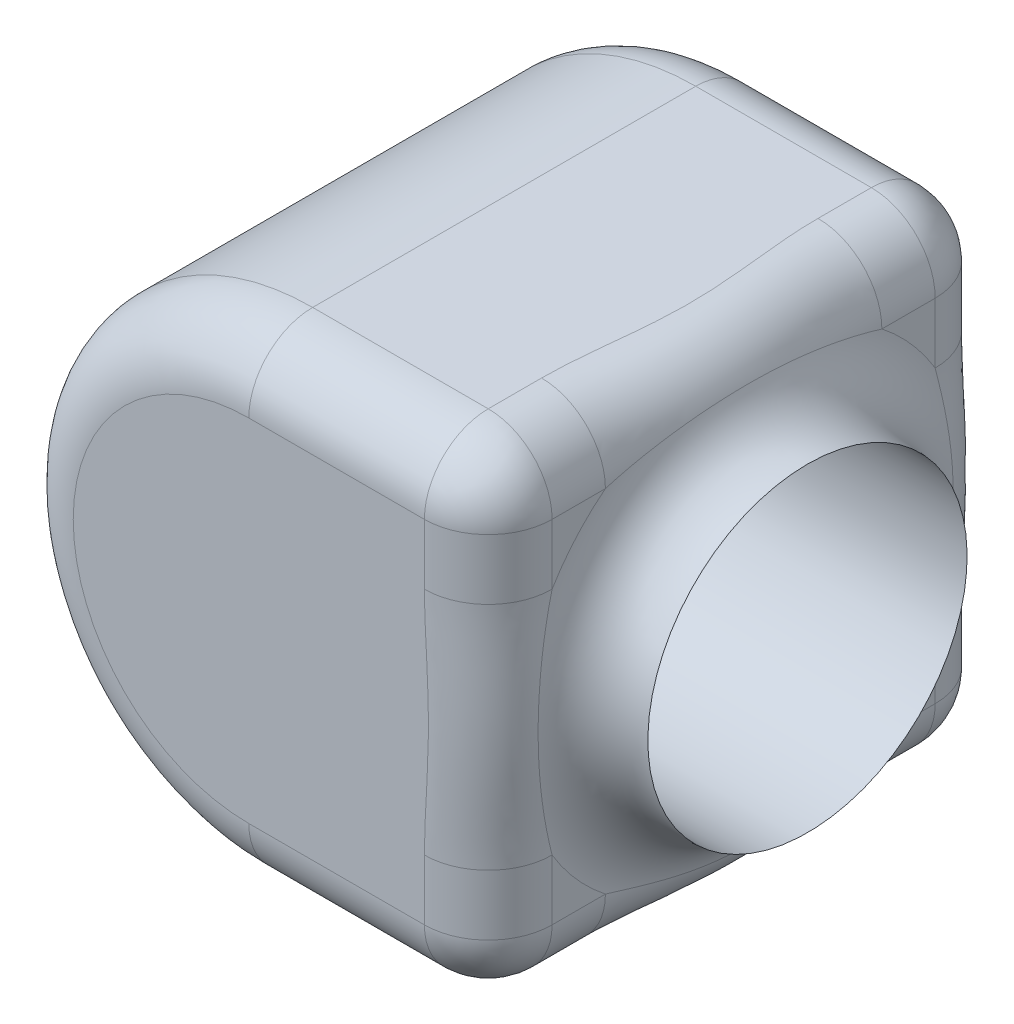
SolidWorks part; units mm, degrees
material "PC 高粘度"
ref_plane "前视基准面" through (0, 0, 0) normal (0, 0, 1) x (1, 0, 0)
ref_plane "上视基准面" through (0, 0, 0) normal (0, 1, 0) x (1, 0, 0)
ref_plane "右视基准面" through (0, 0, 0) normal (1, 0, 0) x (0, 0, -1)
sketch "草图1" plane through (0, 0, 0) normal (0, 0, 1) x (1, 0, 0)
  line L1 (-9.7753, 9.9649) -> (5.2247, 9.9649)
  line L2 (-9.7753, 9.9649) -> (-9.7753, -5.0351)
  line L3 (-9.7753, -5.0351) -> (5.2247, -5.0351)
  line L4 (5.2247, 9.9649) -> (5.2247, -5.0351)
  dimension "D1" = 15
  dimension "D2" = 15
extrude "凸台-拉伸1" add sketch "草图1" along normal blind 16
sketch "草图2" plane through (5.2247, 0, 0) normal (1, 0, 0) x (0, 0, -1)
  line L0 (0, -5.0351) -> (-8, -5.0351)
  line L1 (-16, -5.0351) -> (0, -5.0351) construction
  line L2 (-8, -5.0351) -> (-8, 2.4649)
  circle A0 centre (-8, 2.4649) radius 5
  dimension "D1" = 7.5
extrude "凸台-拉伸2" add sketch "草图2" along normal blind 2 contours A0 region at (5.2247, -0.9706, 4.5645)
fillet "圆角1" radius 2 1 edges at (5.2247, -2.5351, 8)
sketch "草图4" plane through (0, 0, 0) normal (0, 0, -1) x (-1, 0, 0)
  line L0 (-5.2247, -5.0351) -> (-5.2247, 2.4649)
  line L1 (-5.2247, -5.0351) -> (-5.2247, 9.9649) construction
  line L3 (9.7753, -5.0351) -> (9.7753, 9.9649)
  line L4 (9.7753, 9.9649) -> (2.2753, 9.9649)
  line L5 (9.7753, -5.0351) -> (2.2753, -5.0351)
  line L6 (-5.2247, -5.0351) -> (-5.291, -4.9875)
  arc A0 (2.2753, -5.0351) -> (2.2753, 9.9649) centre (2.2753, 2.4649) ccw
  line M2 (9.7753, -5.0351) -> (9.7753, 9.9649)
  line M3 (9.7753, 9.9649) -> (-5.2247, 9.9649)
  line M5 (-5.2247, -5.0351) -> (9.7753, -5.0351)
extrude "切除-拉伸1" cut sketch "草图4" against normal through all and the other way through all contours A0 M5 M2 | A0 L3 M3 region at (-8.1, -3.3599, 0) region at (-8.1, 8.2896, 0)
fillet "圆角2" radius 2 1 edges at (5.2247, -5.0351, 8)
fillet "圆角3" radius 2 10 edges at (1.4747, 9.9649, 0) (-9.7753, 2.4649, 0) (0.4747, -5.0351, 0) (4.6389, -4.4493, 0) (5.2247, 3.4649, 0) (-9.7753, 2.4649, 16) (1.4747, 9.9649, 16) (5.2247, 3.4649, 16) (4.6389, -4.4493, 16) (0.4747, -5.0351, 16)
fillet "圆角4" radius 2 3 edges at (4.6389, 9.3791, 15.4142) (4.6389, 9.3791, 0.5858) (5.2247, 9.9649, 8)
sketch "草图5" plane through (7.2247, 0, 0) normal (1, 0, 0) x (0, 0, -1)
  circle A0 centre (-8, 2.4649) radius 5
extrude "切除-拉伸2" cut sketch "草图5" against normal blind 15
